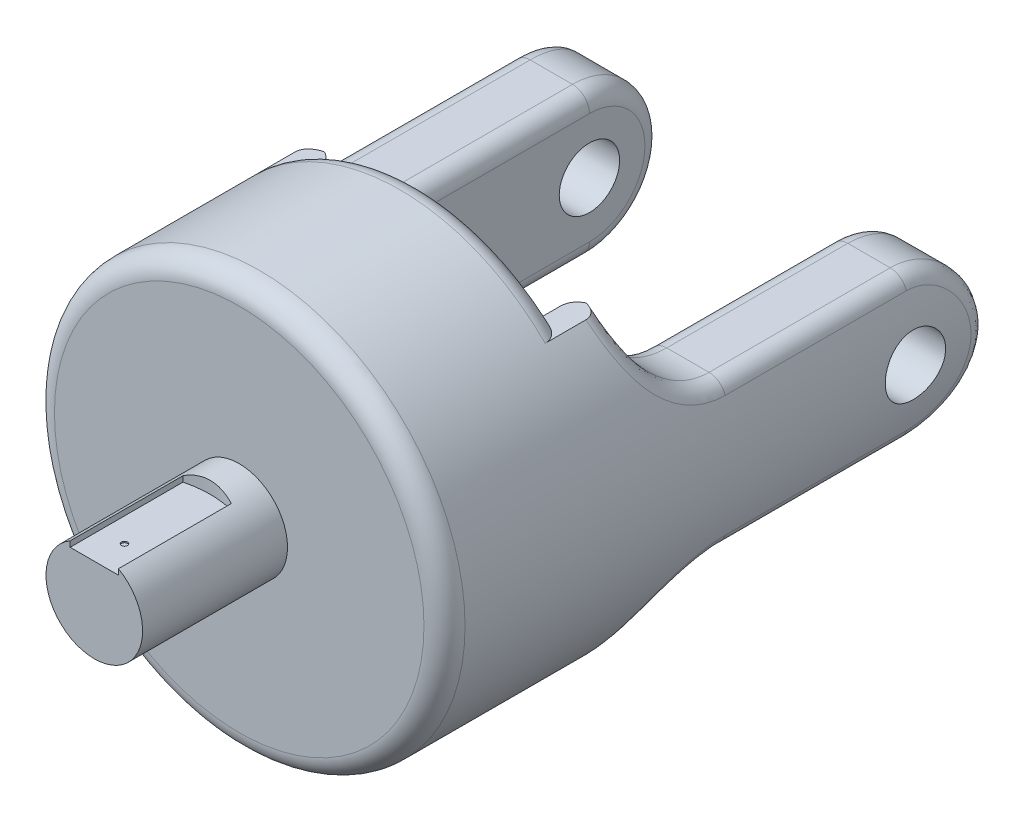
SolidWorks part; units mm, degrees
material "Ductile Iron (SN)"
ref_plane "Front Plane" through (0, 0, 0) normal (0, 0, 1) x (1, 0, 0)
ref_plane "Top Plane" through (0, 0, 0) normal (0, 1, 0) x (1, 0, 0)
ref_plane "Right Plane" through (0, 0, 0) normal (1, 0, 0) x (0, 0, -1)
sketch "Sketch2" plane through (0, 0, 0) normal (0, 0, 1) x (1, 0, 0)
  circle A0 centre (0, 0) radius 17
  dimension "D1" = 34
extrude "Boss-Extrude1" add sketch "Sketch2" along normal blind 45
sketch "Sketch3" plane through (0, 0, 0) normal (0, 1, 0) x (1, 0, 0)
  line L0 (17, 0) -> (-17, 0) construction
  line L1 (-10, 0) -> (10, 0)
  line L2 (-10, 0) -> (-10, -30)
  line L3 (-10, -30) -> (10, -30)
  line L4 (10, 0) -> (10, -30)
  line L5 (-10, 0) -> (10, -30) construction
  line L6 (-10, -30) -> (10, 0) construction
  point P0 (0, -15)
  dimension "D1" = 20
  dimension "D2" = 30
  dimension "D3" = 15
extrude "Cut-Extrude1" cut sketch "Sketch3" against normal mid plane 40
sketch "Sketch4" plane through (0, 0, 0) normal (1, 0, 0) x (0, 0, -1)
  line L0 (26.7759, 0) -> (-60.0941, 0) construction
  line L1 (0, -13.7477) -> (0, 13.7477) construction
  line L20 (-6, 6) -> (-21, 6)
  line L26 (-30, 22) -> (4, 22)
  line L27 (4, 22) -> (4, -22)
  line L28 (4, 0) -> (0, 0)
  line L29 (-27, 12) -> (-30, 12)
  line L31 (-30, 12) -> (-30, 22)
  line L32 (-6, -6) -> (-21, -6)
  line L33 (-30, -22) -> (4, -22)
  line L34 (-30, -12) -> (-30, -22)
  line L35 (-27, -12) -> (-30, -12)
  arc A3 (-6, -6) -> (-6, 6) centre (-6, 0) ccw
  arc A5 (-21, 6) -> (-27, 12) centre (-21, 12) cw
  arc A6 (-21, -6) -> (-27, -12) centre (-21, -12) ccw
  dimension "D1" = 6
  dimension "D3" = 3
  dimension "D4" = 15
  dimension "D2" = 30
  dimension "D5" = 6
  dimension "D6" = 34
  dimension "D7" = 10
extrude "Cut-Extrude5" cut sketch "Sketch4" against normal mid plane 40 contours A5 L20 A3 L28 L27 L26 L31 L29 | L32 A6 L35 L34 L33 L27 L28 A3 region at (0, 13.646, 11.4966) region at (0, -13.646, 11.4966)
sketch "Sketch6" plane through (0, 0, 0) normal (1, 0, 0) x (0, 0, -1)
  circle A0 centre (-6, 0) radius 2.5
  dimension "D1" = 5
extrude "Cut-Extrude7" cut sketch "Sketch6" against normal mid plane 50
sketch "Sketch7" plane through (0, 0, 45) normal (0, 0, 1) x (1, 0, 0)
  circle A0 centre (0, 0) radius 4
  dimension "D1" = 8
extrude "Boss-Extrude2" add sketch "Sketch7" along normal blind 12
ref_plane "Plane1" through (0, 4, 0) normal (0, 1, 0) x (1, 0, 0)
sketch "Sketch9" plane through (0, 4, 0) normal (0, 1, 0) x (1, 0, 0)
  line L0 (0, -57) -> (0, -45) construction
  line L1 (-4, -57) -> (4, -57) construction
  line L2 (-17, -45) -> (17, -45) construction
  line L3 (-2, -57) -> (2, -57)
  line L4 (2, -57) -> (2, -47.654)
  line L5 (-2, -47.654) -> (-2, -57)
  arc A2 (-2, -47.654) -> (2, -47.654) centre (0, -55.4) cw
  dimension "D3" = 8
  dimension "D1" = 2
  dimension "D2" = 2
  dimension "D4" = 1.6
extrude "Cut-Extrude10" cut sketch "Sketch9" against normal blind 1
sketch "Sketch10" plane through (0, 3, 0) normal (0, 1, 0) x (1, 0, 0)
  line L0 (-2, -57) -> (2, -57) construction
  line L1 (-2, -57) -> (-2, -47.654) construction
  circle A0 centre (0, -54.5) radius 0.25
  dimension "D1" = 0.5
  dimension "D2" = 2.5
  dimension "D3" = 2
extrude "Cut-Extrude11" cut sketch "Sketch10" against normal blind 0.1
fillet "Fillet2" radius 1.7 3 edges at (17, 0, 45) (0, -17, 30) (0, 17, 30)
fillet "Fillet3" radius 1.4 20 edges at (14.9515, 8.0902, 25.5512) (14.9515, -8.0902, 25.5512) (15.906, -6, 13.5) (16.992, -0.5203, 0.0226) (10, -7.7574, 25.2426) (10, -6, 13.5) (10, 0, 0) (10, 7.7574, 25.2426) (-15.4292, -7.1373, 24.5148) (-15.906, -6, 13.5) (-17, 0, 0) (-15.4292, 7.1373, 24.5148) (-10, 7.7574, 25.2426) (-10, -7.7574, 25.2426) (-10, -6, 13.5) (-10, 0, 0) (15.906, 6, 13.5) (10, 6, 13.5) (-15.906, 6, 13.5) (-10, 6, 13.5)
